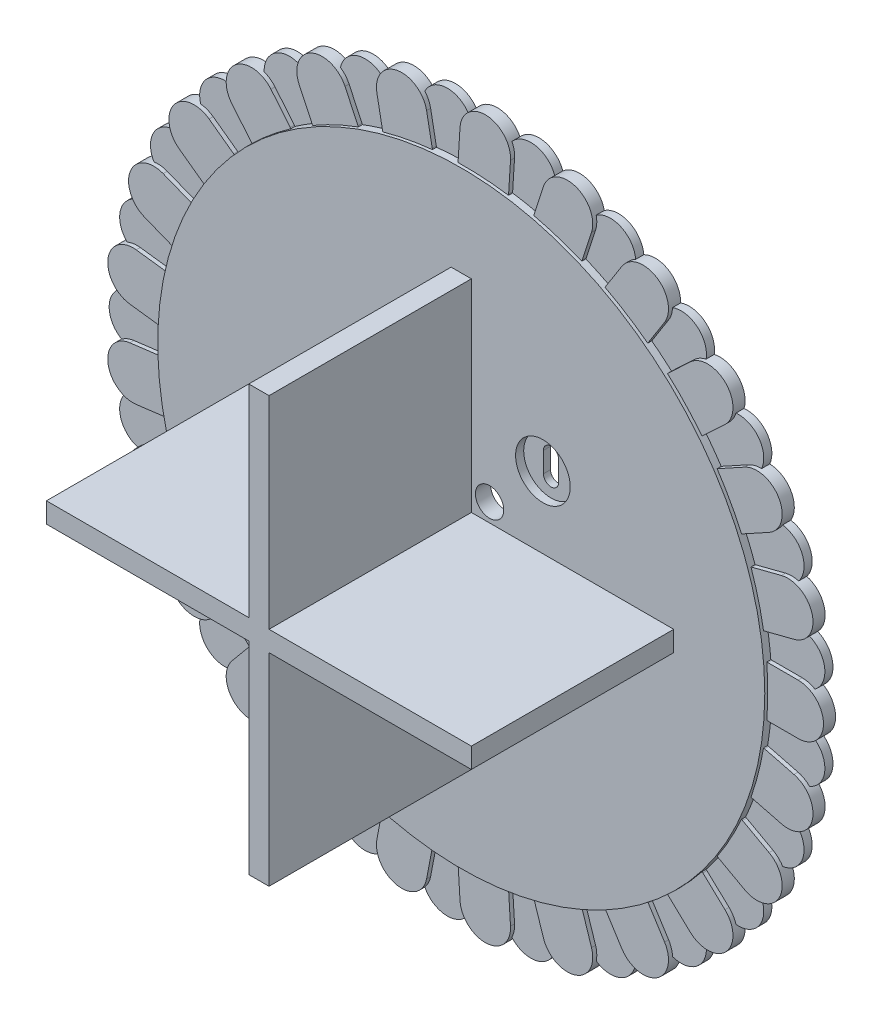
SolidWorks part; units mm, degrees
ref_plane "Front Plane" through (0, 0, 0) normal (0, 0, 1) x (1, 0, 0)
ref_plane "Top Plane" through (0, 0, 0) normal (0, 1, 0) x (1, 0, 0)
ref_plane "Right Plane" through (0, 0, 0) normal (1, 0, 0) x (0, 0, -1)
sketch "Schizzo1" plane through (0, 0, 0) normal (0, 0, 1) x (1, 0, 0)
  circle A0 centre (0, 0) radius 30
  dimension "D1" = 60
extrude "Estrusione-Estrusione1" add sketch "Schizzo1" along normal blind 1.5
sketch "Schizzo2" plane through (0, 0, 1.5) normal (0, 0, 1) x (1, 0, 0)
  line L0 (-1, 1) -> (-1, 21)
  line L1 (-21, 1) -> (-1, 1)
  line L2 (-21, 1) -> (-21, -1)
  line L3 (-21, -1) -> (-1, -1)
  line L4 (21, 1) -> (21, -1)
  line L5 (-1, 1) -> (1, -1) construction
  line L7 (1, -21) -> (-1, -21)
  line L8 (1, -21) -> (1, -1)
  line L9 (1, 21) -> (-1, 21)
  line L10 (-1, -21) -> (-1, -1)
  line L15 (1, 1) -> (1, 21)
  line L18 (1, 1) -> (21, 1)
  line L19 (1, -1) -> (21, -1)
  point P0 (0, 0)
  point P6 (0, 0)
  point P11 (0, 0)
  dimension "D1" = 20
  dimension "D2" = 2
extrude "Estrusione-Estrusione2" add sketch "Schizzo2" along normal blind 20
sketch "Schizzo5" plane through (0, 0, 0) normal (0, 0, -1) x (-1, 0, 0)
  line L0 (-30, 0) -> (-33, 0) construction
  line L1 (-30, -2.5) -> (-33, -2.5)
  line L2 (-30, 2.5) -> (-33, 2.5)
  line L3 (-29.4501, 6.2403) -> (-32.4265, 6.6163)
  line L4 (-30.0768, 1.2797) -> (-33.0531, 1.6557)
  line L5 (-29.7634, 3.76) -> (-32.7398, 4.136) construction
  line L6 (-28.4358, 9.8822) -> (-31.3415, 10.6282)
  line L7 (-29.6792, 5.0392) -> (-32.585, 5.7853)
  line L8 (-29.0575, 7.4607) -> (-31.9632, 8.2068) construction
  line L9 (-26.973, 13.3682) -> (-29.7623, 14.4726)
  line L10 (-28.8136, 8.7193) -> (-31.6029, 9.8237)
  line L11 (-27.8933, 11.0437) -> (-30.6826, 12.1481) construction
  line L12 (-25.0848, 16.6434) -> (-27.7137, 18.0886)
  line L13 (-27.4936, 12.2618) -> (-30.1225, 13.7071)
  line L14 (-26.2892, 14.4526) -> (-28.9181, 15.8979) construction
  line L15 (-22.801, 19.6561) -> (-25.2281, 21.4195)
  line L16 (-25.74, 15.611) -> (-28.167, 17.3744)
  line L17 (-24.2705, 17.6336) -> (-26.6976, 19.3969) construction
  line L18 (-20.1577, 22.3588) -> (-22.3446, 24.4125)
  line L19 (-23.5804, 18.714) -> (-25.7673, 20.7676)
  line L20 (-21.8691, 20.5364) -> (-24.056, 22.5901) construction
  line L21 (-17.1964, 24.709) -> (-19.1087, 27.0205)
  line L22 (-21.049, 21.5218) -> (-22.9613, 23.8334)
  line L23 (-19.1227, 23.1154) -> (-21.035, 25.4269) construction
  line L24 (-13.964, 26.6694) -> (-15.5715, 29.2024)
  line L25 (-18.1856, 23.9903) -> (-19.7931, 26.5233)
  line L26 (-16.0748, 25.3298) -> (-17.6823, 27.8628) construction
  line L27 (-10.5113, 28.2093) -> (-11.7886, 30.9237)
  line L28 (-15.0354, 26.0804) -> (-16.3128, 28.7948)
  line L29 (-12.7734, 27.1448) -> (-14.0507, 29.8593) construction
  line L30 (-6.8929, 29.3042) -> (-7.8199, 32.1574)
  line L31 (-11.6482, 27.7592) -> (-12.5752, 30.6123)
  line L32 (-9.2705, 28.5317) -> (-10.1976, 31.3849) construction
  line L33 (-3.1657, 29.9371) -> (-3.7279, 32.8839)
  line L34 (-8.0772, 29.0002) -> (-8.6393, 31.947)
  line L35 (-5.6214, 29.4686) -> (-6.1836, 32.4155) construction
  line L36 (0.6114, 30.0978) -> (0.423, 33.0919)
  line L37 (-4.3788, 29.7838) -> (-4.5672, 32.7779)
  line L38 (-1.8837, 29.9408) -> (-2.0721, 32.9349) construction
  line L39 (4.3788, 29.7838) -> (4.5672, 32.7779)
  line L40 (-0.6114, 30.0978) -> (-0.423, 33.0919)
  line L41 (1.8837, 29.9408) -> (2.0721, 32.9349) construction
  line L42 (8.0772, 29.0002) -> (8.6393, 31.947)
  line L43 (3.1657, 29.9371) -> (3.7279, 32.8839)
  line L44 (5.6214, 29.4686) -> (6.1836, 32.4155) construction
  line L45 (11.6482, 27.7592) -> (12.5752, 30.6123)
  line L46 (6.8929, 29.3042) -> (7.8199, 32.1574)
  line L47 (9.2705, 28.5317) -> (10.1976, 31.3849) construction
  line L48 (15.0354, 26.0804) -> (16.3128, 28.7948)
  line L49 (10.5113, 28.2093) -> (11.7886, 30.9237)
  line L50 (12.7734, 27.1448) -> (14.0507, 29.8593) construction
  line L51 (18.1856, 23.9903) -> (19.7931, 26.5233)
  line L52 (13.964, 26.6694) -> (15.5715, 29.2024)
  line L53 (16.0748, 25.3298) -> (17.6823, 27.8628) construction
  line L54 (21.049, 21.5218) -> (22.9613, 23.8334)
  line L55 (17.1964, 24.709) -> (19.1087, 27.0205)
  line L56 (19.1227, 23.1154) -> (21.035, 25.4269) construction
  line L57 (23.5804, 18.714) -> (25.7673, 20.7676)
  line L58 (20.1577, 22.3588) -> (22.3446, 24.4125)
  line L59 (21.8691, 20.5364) -> (24.056, 22.5901) construction
  line L60 (25.74, 15.611) -> (28.167, 17.3744)
  line L61 (22.801, 19.6561) -> (25.2281, 21.4195)
  line L62 (24.2705, 17.6336) -> (26.6976, 19.3969) construction
  line L63 (27.4936, 12.2618) -> (30.1225, 13.7071)
  line L64 (25.0848, 16.6434) -> (27.7137, 18.0886)
  line L65 (26.2892, 14.4526) -> (28.9181, 15.8979) construction
  line L66 (28.8136, 8.7193) -> (31.6029, 9.8237)
  line L67 (26.973, 13.3682) -> (29.7623, 14.4726)
  line L68 (27.8933, 11.0437) -> (30.6826, 12.1481) construction
  line L69 (29.6792, 5.0392) -> (32.585, 5.7853)
  line L70 (28.4358, 9.8822) -> (31.3415, 10.6282)
  line L71 (29.0575, 7.4607) -> (31.9632, 8.2068) construction
  line L72 (30.0768, 1.2797) -> (33.0531, 1.6557)
  line L73 (29.4501, 6.2403) -> (32.4265, 6.6163)
  line L74 (29.7634, 3.76) -> (32.7398, 4.136) construction
  line L75 (30, -2.5) -> (33, -2.5)
  line L76 (30, 2.5) -> (33, 2.5)
  line L77 (30, 0) -> (33, 0) construction
  line L78 (29.4501, -6.2403) -> (32.4265, -6.6163)
  line L79 (30.0768, -1.2797) -> (33.0531, -1.6557)
  line L80 (29.7634, -3.76) -> (32.7398, -4.136) construction
  line L81 (28.4358, -9.8822) -> (31.3415, -10.6282)
  line L82 (29.6792, -5.0392) -> (32.585, -5.7853)
  line L83 (29.0575, -7.4607) -> (31.9632, -8.2068) construction
  line L84 (26.973, -13.3682) -> (29.7623, -14.4726)
  line L85 (28.8136, -8.7193) -> (31.6029, -9.8237)
  line L86 (27.8933, -11.0437) -> (30.6826, -12.1481) construction
  line L87 (25.0848, -16.6434) -> (27.7137, -18.0886)
  line L88 (27.4936, -12.2618) -> (30.1225, -13.7071)
  line L89 (26.2892, -14.4526) -> (28.9181, -15.8979) construction
  line L90 (22.801, -19.6561) -> (25.2281, -21.4195)
  line L91 (25.74, -15.611) -> (28.167, -17.3744)
  line L92 (24.2705, -17.6336) -> (26.6976, -19.3969) construction
  line L93 (20.1577, -22.3588) -> (22.3446, -24.4125)
  line L94 (23.5804, -18.714) -> (25.7673, -20.7676)
  line L95 (21.8691, -20.5364) -> (24.056, -22.5901) construction
  line L96 (17.1964, -24.709) -> (19.1087, -27.0205)
  line L97 (21.049, -21.5218) -> (22.9613, -23.8334)
  line L98 (19.1227, -23.1154) -> (21.035, -25.4269) construction
  line L99 (13.964, -26.6694) -> (15.5715, -29.2024)
  line L100 (18.1856, -23.9903) -> (19.7931, -26.5233)
  line L101 (16.0748, -25.3298) -> (17.6823, -27.8628) construction
  line L102 (10.5113, -28.2093) -> (11.7886, -30.9237)
  line L103 (15.0354, -26.0804) -> (16.3128, -28.7948)
  line L104 (12.7734, -27.1448) -> (14.0507, -29.8593) construction
  line L105 (6.8929, -29.3042) -> (7.8199, -32.1574)
  line L106 (11.6482, -27.7592) -> (12.5752, -30.6123)
  line L107 (9.2705, -28.5317) -> (10.1976, -31.3849) construction
  line L108 (3.1657, -29.9371) -> (3.7279, -32.8839)
  line L109 (8.0772, -29.0002) -> (8.6393, -31.947)
  line L110 (5.6214, -29.4686) -> (6.1836, -32.4155) construction
  line L111 (-0.6114, -30.0978) -> (-0.423, -33.0919)
  line L112 (4.3788, -29.7838) -> (4.5672, -32.7779)
  line L113 (1.8837, -29.9408) -> (2.0721, -32.9349) construction
  line L114 (-4.3788, -29.7838) -> (-4.5672, -32.7779)
  line L115 (0.6114, -30.0978) -> (0.423, -33.0919)
  line L116 (-1.8837, -29.9408) -> (-2.0721, -32.9349) construction
  line L117 (-8.0772, -29.0002) -> (-8.6393, -31.947)
  line L118 (-3.1657, -29.9371) -> (-3.7279, -32.8839)
  line L119 (-5.6214, -29.4686) -> (-6.1836, -32.4155) construction
  line L120 (-11.6482, -27.7592) -> (-12.5752, -30.6123)
  line L121 (-6.8929, -29.3042) -> (-7.8199, -32.1574)
  line L122 (-9.2705, -28.5317) -> (-10.1976, -31.3849) construction
  line L123 (-15.0354, -26.0804) -> (-16.3128, -28.7948)
  line L124 (-10.5113, -28.2093) -> (-11.7886, -30.9237)
  line L125 (-12.7734, -27.1448) -> (-14.0507, -29.8593) construction
  line L126 (-18.1856, -23.9903) -> (-19.7931, -26.5233)
  line L127 (-13.964, -26.6694) -> (-15.5715, -29.2024)
  line L128 (-16.0748, -25.3298) -> (-17.6823, -27.8628) construction
  line L129 (-21.049, -21.5218) -> (-22.9613, -23.8334)
  line L130 (-17.1964, -24.709) -> (-19.1087, -27.0205)
  line L131 (-19.1227, -23.1154) -> (-21.035, -25.4269) construction
  line L132 (-23.5804, -18.714) -> (-25.7673, -20.7676)
  line L133 (-20.1577, -22.3588) -> (-22.3446, -24.4125)
  line L134 (-21.8691, -20.5364) -> (-24.056, -22.5901) construction
  line L135 (-25.74, -15.611) -> (-28.167, -17.3744)
  line L136 (-22.801, -19.6561) -> (-25.2281, -21.4195)
  line L137 (-24.2705, -17.6336) -> (-26.6976, -19.3969) construction
  line L138 (-27.4936, -12.2618) -> (-30.1225, -13.7071)
  line L139 (-25.0848, -16.6434) -> (-27.7137, -18.0886)
  line L140 (-26.2892, -14.4526) -> (-28.9181, -15.8979) construction
  line L141 (-28.8136, -8.7193) -> (-31.6029, -9.8237)
  line L142 (-26.973, -13.3682) -> (-29.7623, -14.4726)
  line L143 (-27.8933, -11.0437) -> (-30.6826, -12.1481) construction
  line L144 (-29.6792, -5.0392) -> (-32.585, -5.7853)
  line L145 (-28.4358, -9.8822) -> (-31.3415, -10.6282)
  line L146 (-29.0575, -7.4607) -> (-31.9632, -8.2068) construction
  line L147 (-30.0768, -1.2797) -> (-33.0531, -1.6557)
  line L148 (-29.4501, -6.2403) -> (-32.4265, -6.6163)
  line L149 (-29.7634, -3.76) -> (-32.7398, -4.136) construction
  circle A0 centre (0, 0) radius 30 construction
  arc A1 (-30, -2.5) -> (-30, 2.5) centre (-30, 0) ccw
  arc A2 (-33, 2.5) -> (-33, -2.5) centre (-33, 0) ccw
  arc A3 (-30.0768, 1.2797) -> (-29.4501, 6.2403) centre (-29.7634, 3.76) ccw
  arc A4 (-32.4265, 6.6163) -> (-33.0531, 1.6557) centre (-32.7398, 4.136) ccw
  arc A5 (-29.6792, 5.0392) -> (-28.4358, 9.8822) centre (-29.0575, 7.4607) ccw
  arc A6 (-31.3415, 10.6282) -> (-32.585, 5.7853) centre (-31.9632, 8.2068) ccw
  arc A7 (-28.8136, 8.7193) -> (-26.973, 13.3682) centre (-27.8933, 11.0437) ccw
  arc A8 (-29.7623, 14.4726) -> (-31.6029, 9.8237) centre (-30.6826, 12.1481) ccw
  arc A9 (-27.4936, 12.2618) -> (-25.0848, 16.6434) centre (-26.2892, 14.4526) ccw
  arc A10 (-27.7137, 18.0886) -> (-30.1225, 13.7071) centre (-28.9181, 15.8979) ccw
  arc A11 (-25.74, 15.611) -> (-22.801, 19.6561) centre (-24.2705, 17.6336) ccw
  arc A12 (-25.2281, 21.4195) -> (-28.167, 17.3744) centre (-26.6976, 19.3969) ccw
  arc A13 (-23.5804, 18.714) -> (-20.1577, 22.3588) centre (-21.8691, 20.5364) ccw
  arc A14 (-22.3446, 24.4125) -> (-25.7673, 20.7676) centre (-24.056, 22.5901) ccw
  arc A15 (-21.049, 21.5218) -> (-17.1964, 24.709) centre (-19.1227, 23.1154) ccw
  arc A16 (-19.1087, 27.0205) -> (-22.9613, 23.8334) centre (-21.035, 25.4269) ccw
  arc A17 (-18.1856, 23.9903) -> (-13.964, 26.6694) centre (-16.0748, 25.3298) ccw
  arc A18 (-15.5715, 29.2024) -> (-19.7931, 26.5233) centre (-17.6823, 27.8628) ccw
  arc A19 (-15.0354, 26.0804) -> (-10.5113, 28.2093) centre (-12.7734, 27.1448) ccw
  arc A20 (-11.7886, 30.9237) -> (-16.3128, 28.7948) centre (-14.0507, 29.8593) ccw
  arc A21 (-11.6482, 27.7592) -> (-6.8929, 29.3042) centre (-9.2705, 28.5317) ccw
  arc A22 (-7.8199, 32.1574) -> (-12.5752, 30.6123) centre (-10.1976, 31.3849) ccw
  arc A23 (-8.0772, 29.0002) -> (-3.1657, 29.9371) centre (-5.6214, 29.4686) ccw
  arc A24 (-3.7279, 32.8839) -> (-8.6393, 31.947) centre (-6.1836, 32.4155) ccw
  arc A25 (-4.3788, 29.7838) -> (0.6114, 30.0978) centre (-1.8837, 29.9408) ccw
  arc A26 (0.423, 33.0919) -> (-4.5672, 32.7779) centre (-2.0721, 32.9349) ccw
  arc A27 (-0.6114, 30.0978) -> (4.3788, 29.7838) centre (1.8837, 29.9408) ccw
  arc A28 (4.5672, 32.7779) -> (-0.423, 33.0919) centre (2.0721, 32.9349) ccw
  arc A29 (3.1657, 29.9371) -> (8.0772, 29.0002) centre (5.6214, 29.4686) ccw
  arc A30 (8.6393, 31.947) -> (3.7279, 32.8839) centre (6.1836, 32.4155) ccw
  arc A31 (6.8929, 29.3042) -> (11.6482, 27.7592) centre (9.2705, 28.5317) ccw
  arc A32 (12.5752, 30.6123) -> (7.8199, 32.1574) centre (10.1976, 31.3849) ccw
  arc A33 (10.5113, 28.2093) -> (15.0354, 26.0804) centre (12.7734, 27.1448) ccw
  arc A34 (16.3128, 28.7948) -> (11.7886, 30.9237) centre (14.0507, 29.8593) ccw
  arc A35 (13.964, 26.6694) -> (18.1856, 23.9903) centre (16.0748, 25.3298) ccw
  arc A36 (19.7931, 26.5233) -> (15.5715, 29.2024) centre (17.6823, 27.8628) ccw
  arc A37 (17.1964, 24.709) -> (21.049, 21.5218) centre (19.1227, 23.1154) ccw
  arc A38 (22.9613, 23.8334) -> (19.1087, 27.0205) centre (21.035, 25.4269) ccw
  arc A39 (20.1577, 22.3588) -> (23.5804, 18.714) centre (21.8691, 20.5364) ccw
  arc A40 (25.7673, 20.7676) -> (22.3446, 24.4125) centre (24.056, 22.5901) ccw
  arc A41 (22.801, 19.6561) -> (25.74, 15.611) centre (24.2705, 17.6336) ccw
  arc A42 (28.167, 17.3744) -> (25.2281, 21.4195) centre (26.6976, 19.3969) ccw
  arc A43 (25.0848, 16.6434) -> (27.4936, 12.2618) centre (26.2892, 14.4526) ccw
  arc A44 (30.1225, 13.7071) -> (27.7137, 18.0886) centre (28.9181, 15.8979) ccw
  arc A45 (26.973, 13.3682) -> (28.8136, 8.7193) centre (27.8933, 11.0437) ccw
  arc A46 (31.6029, 9.8237) -> (29.7623, 14.4726) centre (30.6826, 12.1481) ccw
  arc A47 (28.4358, 9.8822) -> (29.6792, 5.0392) centre (29.0575, 7.4607) ccw
  arc A48 (32.585, 5.7853) -> (31.3415, 10.6282) centre (31.9632, 8.2068) ccw
  arc A49 (29.4501, 6.2403) -> (30.0768, 1.2797) centre (29.7634, 3.76) ccw
  arc A50 (33.0531, 1.6557) -> (32.4265, 6.6163) centre (32.7398, 4.136) ccw
  arc A51 (30, 2.5) -> (30, -2.5) centre (30, 0) ccw
  arc A52 (33, -2.5) -> (33, 2.5) centre (33, 0) ccw
  arc A53 (30.0768, -1.2797) -> (29.4501, -6.2403) centre (29.7634, -3.76) ccw
  arc A54 (32.4265, -6.6163) -> (33.0531, -1.6557) centre (32.7398, -4.136) ccw
  arc A55 (29.6792, -5.0392) -> (28.4358, -9.8822) centre (29.0575, -7.4607) ccw
  arc A56 (31.3415, -10.6282) -> (32.585, -5.7853) centre (31.9632, -8.2068) ccw
  arc A57 (28.8136, -8.7193) -> (26.973, -13.3682) centre (27.8933, -11.0437) ccw
  arc A58 (29.7623, -14.4726) -> (31.6029, -9.8237) centre (30.6826, -12.1481) ccw
  arc A59 (27.4936, -12.2618) -> (25.0848, -16.6434) centre (26.2892, -14.4526) ccw
  arc A60 (27.7137, -18.0886) -> (30.1225, -13.7071) centre (28.9181, -15.8979) ccw
  arc A61 (25.74, -15.611) -> (22.801, -19.6561) centre (24.2705, -17.6336) ccw
  arc A62 (25.2281, -21.4195) -> (28.167, -17.3744) centre (26.6976, -19.3969) ccw
  arc A63 (23.5804, -18.714) -> (20.1577, -22.3588) centre (21.8691, -20.5364) ccw
  arc A64 (22.3446, -24.4125) -> (25.7673, -20.7676) centre (24.056, -22.5901) ccw
  arc A65 (21.049, -21.5218) -> (17.1964, -24.709) centre (19.1227, -23.1154) ccw
  arc A66 (19.1087, -27.0205) -> (22.9613, -23.8334) centre (21.035, -25.4269) ccw
  arc A67 (18.1856, -23.9903) -> (13.964, -26.6694) centre (16.0748, -25.3298) ccw
  arc A68 (15.5715, -29.2024) -> (19.7931, -26.5233) centre (17.6823, -27.8628) ccw
  arc A69 (15.0354, -26.0804) -> (10.5113, -28.2093) centre (12.7734, -27.1448) ccw
  arc A70 (11.7886, -30.9237) -> (16.3128, -28.7948) centre (14.0507, -29.8593) ccw
  arc A71 (11.6482, -27.7592) -> (6.8929, -29.3042) centre (9.2705, -28.5317) ccw
  arc A72 (7.8199, -32.1574) -> (12.5752, -30.6123) centre (10.1976, -31.3849) ccw
  arc A73 (8.0772, -29.0002) -> (3.1657, -29.9371) centre (5.6214, -29.4686) ccw
  arc A74 (3.7279, -32.8839) -> (8.6393, -31.947) centre (6.1836, -32.4155) ccw
  arc A75 (4.3788, -29.7838) -> (-0.6114, -30.0978) centre (1.8837, -29.9408) ccw
  arc A76 (-0.423, -33.0919) -> (4.5672, -32.7779) centre (2.0721, -32.9349) ccw
  arc A77 (0.6114, -30.0978) -> (-4.3788, -29.7838) centre (-1.8837, -29.9408) ccw
  arc A78 (-4.5672, -32.7779) -> (0.423, -33.0919) centre (-2.0721, -32.9349) ccw
  arc A79 (-3.1657, -29.9371) -> (-8.0772, -29.0002) centre (-5.6214, -29.4686) ccw
  arc A80 (-8.6393, -31.947) -> (-3.7279, -32.8839) centre (-6.1836, -32.4155) ccw
  arc A81 (-6.8929, -29.3042) -> (-11.6482, -27.7592) centre (-9.2705, -28.5317) ccw
  arc A82 (-12.5752, -30.6123) -> (-7.8199, -32.1574) centre (-10.1976, -31.3849) ccw
  arc A83 (-10.5113, -28.2093) -> (-15.0354, -26.0804) centre (-12.7734, -27.1448) ccw
  arc A84 (-16.3128, -28.7948) -> (-11.7886, -30.9237) centre (-14.0507, -29.8593) ccw
  arc A85 (-13.964, -26.6694) -> (-18.1856, -23.9903) centre (-16.0748, -25.3298) ccw
  arc A86 (-19.7931, -26.5233) -> (-15.5715, -29.2024) centre (-17.6823, -27.8628) ccw
  arc A87 (-17.1964, -24.709) -> (-21.049, -21.5218) centre (-19.1227, -23.1154) ccw
  arc A88 (-22.9613, -23.8334) -> (-19.1087, -27.0205) centre (-21.035, -25.4269) ccw
  arc A89 (-20.1577, -22.3588) -> (-23.5804, -18.714) centre (-21.8691, -20.5364) ccw
  arc A90 (-25.7673, -20.7676) -> (-22.3446, -24.4125) centre (-24.056, -22.5901) ccw
  arc A91 (-22.801, -19.6561) -> (-25.74, -15.611) centre (-24.2705, -17.6336) ccw
  arc A92 (-28.167, -17.3744) -> (-25.2281, -21.4195) centre (-26.6976, -19.3969) ccw
  arc A93 (-25.0848, -16.6434) -> (-27.4936, -12.2618) centre (-26.2892, -14.4526) ccw
  arc A94 (-30.1225, -13.7071) -> (-27.7137, -18.0886) centre (-28.9181, -15.8979) ccw
  arc A95 (-26.973, -13.3682) -> (-28.8136, -8.7193) centre (-27.8933, -11.0437) ccw
  arc A96 (-31.6029, -9.8237) -> (-29.7623, -14.4726) centre (-30.6826, -12.1481) ccw
  arc A97 (-28.4358, -9.8822) -> (-29.6792, -5.0392) centre (-29.0575, -7.4607) ccw
  arc A98 (-32.585, -5.7853) -> (-31.3415, -10.6282) centre (-31.9632, -8.2068) ccw
  arc A99 (-29.4501, -6.2403) -> (-30.0768, -1.2797) centre (-29.7634, -3.76) ccw
  arc A100 (-33.0531, -1.6557) -> (-32.4265, -6.6163) centre (-32.7398, -4.136) ccw
  point P6 (-31.5, 0)
  point P16 (-31.2516, 3.948)
  point P23 (-30.5104, 7.8337)
  point P30 (-29.288, 11.5959)
  point P37 (-27.6037, 15.1752)
  point P44 (-25.484, 18.5152)
  point P51 (-22.9625, 21.5632)
  point P58 (-20.0789, 24.2712)
  point P65 (-16.8785, 26.5963)
  point P72 (-13.412, 28.5021)
  point P79 (-9.734, 29.9583)
  point P86 (-5.9025, 30.942)
  point P93 (-1.9779, 31.4378)
  point P100 (1.9779, 31.4378)
  point P107 (5.9025, 30.942)
  point P114 (9.734, 29.9583)
  point P121 (13.412, 28.5021)
  point P128 (16.8785, 26.5963)
  point P135 (20.0789, 24.2712)
  point P142 (22.9625, 21.5632)
  point P149 (25.484, 18.5152)
  point P156 (27.6037, 15.1752)
  point P163 (29.288, 11.5959)
  point P170 (30.5104, 7.8337)
  point P177 (31.2516, 3.948)
  point P184 (31.5, 0)
  point P191 (31.2516, -3.948)
  point P198 (30.5104, -7.8337)
  point P205 (29.288, -11.5959)
  point P212 (27.6037, -15.1752)
  point P219 (25.484, -18.5152)
  point P226 (22.9625, -21.5632)
  point P233 (20.0789, -24.2712)
  point P240 (16.8785, -26.5963)
  point P247 (13.412, -28.5021)
  point P254 (9.734, -29.9583)
  point P261 (5.9025, -30.942)
  point P268 (1.9779, -31.4378)
  point P275 (-1.9779, -31.4378)
  point P282 (-5.9025, -30.942)
  point P289 (-9.734, -29.9583)
  point P296 (-13.412, -28.5021)
  point P303 (-16.8785, -26.5963)
  point P310 (-20.0789, -24.2712)
  point P317 (-22.9625, -21.5632)
  point P324 (-25.484, -18.5152)
  point P331 (-27.6037, -15.1752)
  point P338 (-29.288, -11.5959)
  point P345 (-30.5104, -7.8337)
  point P352 (-31.2516, -3.948)
  point P357 (0, 0)
  circle M206 centre (0, 0) radius 30
  dimension "D1" = 5
  dimension "D2" = 3
  dimension "D4" = 4.136
  dimension "D5" = 0.2602
  dimension "D3" = 50
extrude "Estrusione-Estrusione3" add sketch "Schizzo5" against normal blind 0.8 contours A6 A4 A2 L2 A1 A5 L7 M206 | A10 A8 A6 L6 A5 A9 L13 M206 | A14 A12 A10 L12 A9 A13 L19 M206 | A18 A16 A14 L18 A13 A17 L25 M206 | A22 A20 A18 L24 A17 A21 L31 M206 | A26 A24 A22 L30 A21 A25 L37 M206 | A30 A28 A26 L36 A25 A29 L43 M206 | A34 A32 A30 L42 A29 A33 L49 M206 | A38 A36 A34 L48 A33 A37 L55 M206 | A42 A40 A38 L54 A37 A41 L61 M206 | A46 A44 A42 L60 A41 A45 L67 M206 | A50 A48 A46 L66 A45 A49 L73 M206 | A54 A52 A50 L72 A49 A53 L79 M206 | A58 A56 A54 L78 A53 A57 L85 M206 | A62 A60 A58 L84 A57 A61 L91 M206 | A66 A64 A62 L90 A61 A65 L97 M206 | A70 A68 A66 L96 A65 A69 L103 M206 | A74 A72 A70 L102 A69 A73 L109 M206 | A78 A76 A74 L108 A73 A77 L115 M206 | A82 A80 A78 L114 A77 A81 L121 M206 | A86 A84 A82 L120 A81 A85 L127 M206 | A90 A88 A86 L126 A85 A89 L133 M206 | A94 A92 A90 L132 A89 A93 L139 M206 | A98 A96 A94 L138 A93 A97 L145 M206 | A2 A100 A98 L144 A97 A1 L1 M206 region at (32.5734, -4.115, 0) region at (32.5734, 4.115, 0) region at (30.5267, -12.0864, 0) region at (30.5267, 12.0864, 0) region at (26.5619, -19.2983, 0) region at (26.5619, 19.2983, 0) region at (20.9281, -25.2977, 0) region at (20.9281, 25.2977, 0) region at (13.9793, -29.7075, 0) region at (13.9793, 29.7075, 0) region at (6.1522, -32.2507, 0) region at (6.1522, 32.2507, 0) region at (-2.0616, -32.7675, 0) region at (-2.0616, 32.7675, 0) region at (-10.1457, -31.2254, 0) region at (-10.1457, 31.2254, 0) region at (-17.5924, -27.7212, 0) region at (-17.5924, 27.7212, 0) region at (-23.9337, -22.4752, 0) region at (-23.9337, 22.4752, 0) region at (-28.7711, -15.8171, 0) region at (-28.7711, 15.8171, 0) region at (-31.8008, -8.1651, 0) region at (-31.8008, 8.1651, 0) region at (-32.8323, 0, 0)
extrude "Estrusione-Estrusione4" add sketch "Schizzo5<3>" against normal blind 1.2 contours A9 L12 A10 L13 | A13 L18 A14 L19 | A17 L24 A18 L25 | A21 L30 A22 L31 | A25 L36 A26 L37 | A29 L42 A30 L43 | A33 L48 A34 L49 | A37 L54 A38 L55 | A41 L60 A42 L61 | A45 L66 A46 L67 | A49 L72 A50 L73 | A53 L78 A54 L79 | A57 L84 A58 L85 | A61 L90 A62 L91 | A65 L96 A66 L97 | A69 L102 A70 L103 | A73 L108 A74 L109 | A77 L114 A78 L115 | A81 L120 A82 L121 | A85 L126 A86 L127 | A89 L132 A90 L133 | A93 L138 A94 L139 | A97 L144 A98 L145 | A1 L2 A2 L1 | A5 L6 A6 L7
sketch "Schizzo5<3>" plane through (0, 0, 0) normal (0, 0, -1) x (-1, 0, 0) same geometry as "Schizzo5"
sketch "Schizzo6" plane through (0, 0, 1.5) normal (0, 0, 1) x (1, 0, 0)
  line L0 (-22.5607, 0) -> (21.4273, 0) construction
  line L1 (0, 12.6583) -> (0, -8.7601) construction
  circle A0 centre (-2.8, 2.8) radius 1.4
  circle A1 centre (-2.8, -2.8) radius 1.4
  circle A2 centre (2.8, -2.8) radius 1.4
  circle A3 centre (2.8, 2.8) radius 1.4
  dimension "D3" = 2.8
  dimension "D1" = 2.8
  dimension "D2" = 2.8
extrude "Taglio-Estrusione3" cut sketch "Schizzo6" against normal through all
sketch "Schizzo7" plane through (0, 0, 1.5) normal (0, 0, 1) x (1, 0, 0)
  line L0 (-21, 0) -> (21, 0) construction
  line L1 (-21, 1) -> (-21, -1) construction
  line L2 (21, -1) -> (21, 1) construction
  line L3 (0, 21) -> (0, -21) construction
  line L4 (1, 21) -> (-1, 21) construction
  line L5 (-1, -21) -> (1, -21) construction
  line L6 (-8.0711, 8.0711) -> (0, 0) construction
  circle A0 centre (-8.0711, 8.0711) radius 2.7
  circle A1 centre (-8.0711, -8.0711) radius 2.7
  circle A2 centre (8.0711, -8.0711) radius 2.7
  circle A3 centre (8.0711, 8.0711) radius 2.7
  dimension "D1" = 10
  dimension "D3" = 5.4
  dimension "D2" = 45
extrude "Taglio-Estrusione4" cut sketch "Schizzo7" against normal blind 0.8
sketch "Schizzo3" plane through (0, 0, 1.5) normal (0, 0, 1) x (1, 0, 0)
  line L0 (-8.0711, 9.0711) -> (-8.0711, 7.0711) construction
  line L1 (-21, 0) -> (21, 0) construction
  line L2 (-0.2637, 0.2637) -> (-1.0137, 1.0137) construction
  line L3 (-7.3211, 9.0711) -> (-7.3211, 7.0711)
  line L4 (-21, 1) -> (-21, -1) construction
  line L5 (21, -1) -> (21, 1) construction
  line L6 (1, 21) -> (-1, 21) construction
  line L7 (0, 21) -> (0, -21) construction
  line L8 (-1, -21) -> (1, -21) construction
  line L9 (-8.8211, 9.0711) -> (-8.8211, 7.0711)
  line L10 (-8.0711, -9.0711) -> (-8.0711, -7.0711) construction
  line L11 (-7.3211, -9.0711) -> (-7.3211, -7.0711)
  line L12 (-8.8211, -9.0711) -> (-8.8211, -7.0711)
  line L13 (8.0711, -9.0711) -> (8.0711, -7.0711) construction
  line L14 (7.3211, -9.0711) -> (7.3211, -7.0711)
  line L15 (8.8211, -9.0711) -> (8.8211, -7.0711)
  line L16 (8.0711, 9.0711) -> (8.0711, 7.0711) construction
  line L17 (7.3211, 9.0711) -> (7.3211, 7.0711)
  line L18 (8.8211, 9.0711) -> (8.8211, 7.0711)
  line L19 (-1, 21) -> (-1, 1) construction
  arc A13 (-7.3211, 9.0711) -> (-8.8211, 9.0711) centre (-8.0711, 9.0711) ccw
  arc A14 (-8.8211, 7.0711) -> (-7.3211, 7.0711) centre (-8.0711, 7.0711) ccw
  arc A15 (-7.3211, -9.0711) -> (-8.8211, -9.0711) centre (-8.0711, -9.0711) cw
  arc A16 (-8.8211, -7.0711) -> (-7.3211, -7.0711) centre (-8.0711, -7.0711) cw
  arc A17 (7.3211, -9.0711) -> (8.8211, -9.0711) centre (8.0711, -9.0711) ccw
  arc A18 (8.8211, -7.0711) -> (7.3211, -7.0711) centre (8.0711, -7.0711) ccw
  arc A19 (7.3211, 9.0711) -> (8.8211, 9.0711) centre (8.0711, 9.0711) cw
  arc A20 (8.8211, 7.0711) -> (7.3211, 7.0711) centre (8.0711, 7.0711) cw
  point P2 (-8.0711, 8.0711)
  point P25 (0, 0)
  point P30 (-8.0711, -8.0711)
  point P41 (8.0711, -8.0711)
  point P48 (8.0711, 8.0711)
  dimension "D1" = 1.5
  dimension "D2" = 2
  dimension "D3" = 10
  dimension "D4" = 7.0711
extrude "Taglio-Estrusione5" cut sketch "Schizzo3" against normal through all
